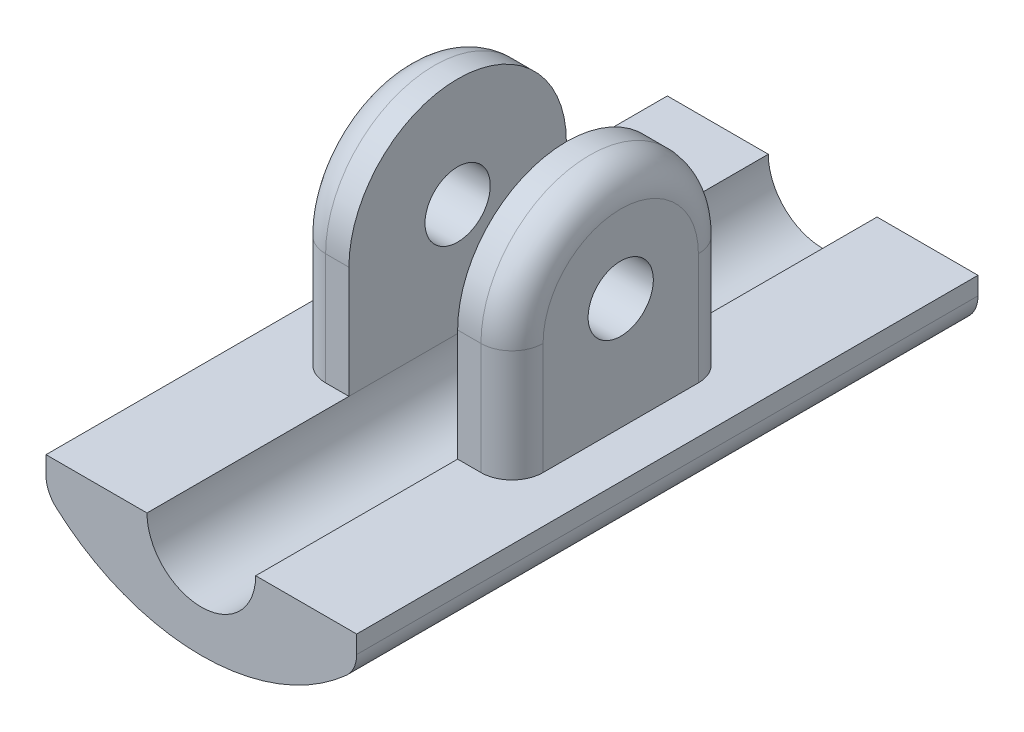
SolidWorks part; units mm, degrees
material "ABS"
ref_plane "Front Plane" through (0, 0, 0) normal (0, 0, 1) x (1, 0, 0)
ref_plane "Top Plane" through (0, 0, 0) normal (0, 1, 0) x (1, 0, 0)
ref_plane "Right Plane" through (0, 0, 0) normal (1, 0, 0) x (0, 0, -1)
sketch "Sketch1" plane through (0, 0, 0) normal (0, 0, 1) x (1, 0, 0)
  line L0 (-10, 0) -> (10, 0)
  line L2 (-10, 0) -> (10, 0)
  line L3 (-10, 0) -> (-10, 2)
  line L4 (-10, 2) -> (10, 2)
  line L5 (10, 0) -> (10, 2)
  arc A0 (10, 0) -> (-10, 0) centre (0, 9.798) cw
  point P4 (0, 0)
  dimension "D1" = 14
  dimension "D2" = 20
  dimension "D3" = 2
extrude "Boss-Extrude1" add sketch "Sketch1" along normal blind 20 and the other way blind 20 contours A0 L0 | L0 L5 L4 L3 region at (0, 1, 0) region at (0, -1.7045, 0)
sketch "Sketch2" plane through (0, 0, 0) normal (1, 0, 0) x (0, 0, -1)
  line L0 (-20, 2) -> (20, 2) construction
  line L1 (-7, 2) -> (7, 2)
  line L2 (-7, 2) -> (-7, 9.2)
  line L3 (-7, 9.2) -> (7, 9.2)
  line L4 (7, 2) -> (7, 9.2)
  circle A0 centre (0, 9.2) radius 7
  circle A2 centre (0, 9.2) radius 2.1
  dimension "D1" = 14
  dimension "D3" = 0
  dimension "D7" = 4.2
  dimension "D2" = 7.2
extrude "Boss-Extrude2" add sketch "Sketch2" along normal blind 7 and the other way blind 7 contours A2 L3 A0 | A2 L3 A0 | A0 L2 L1 L4 region at (0, 5.6, 6.8426) region at (0, 12.3766, 0) region at (0, 6.0234, 0)
sketch "Sketch3" plane through (0, 0, 7) normal (0, 0, 1) x (1, 0, 0)
  line L0 (-7, 2) -> (7, 2) construction
  line L1 (-3.5, 2) -> (3.5, 2)
  line L2 (-3.5, 2) -> (-3.5, 17)
  line L3 (-3.5, 17) -> (3.5, 17)
  line L4 (3.5, 2) -> (3.5, 17)
  dimension "D1" = 7
  dimension "D2" = 3.5
  dimension "D3" = 15
extrude "Cut-Extrude1" cut sketch "Sketch3" against normal blind 60
fillet "Fillet1" radius 2 2 edges at (-10, 0, 0) (10, 0, 0)
sketch "Sketch4" plane through (0, 0, 20) normal (0, 0, 1) x (1, 0, 0)
  line L0 (-10, 2) -> (10, 2) construction
  circle A0 centre (0, 2) radius 3.5
  dimension "D1" = 7
extrude "Cut-Extrude2" cut sketch "Sketch4" against normal blind 60
fillet "Fillet3" radius 2 6 edges at (-7, 5.6, -7) (-7, 5.6, 7) (7, 5.6, -7) (7, 5.6, 7) (-7, 16.2, 0) (7, 16.2, 0)
